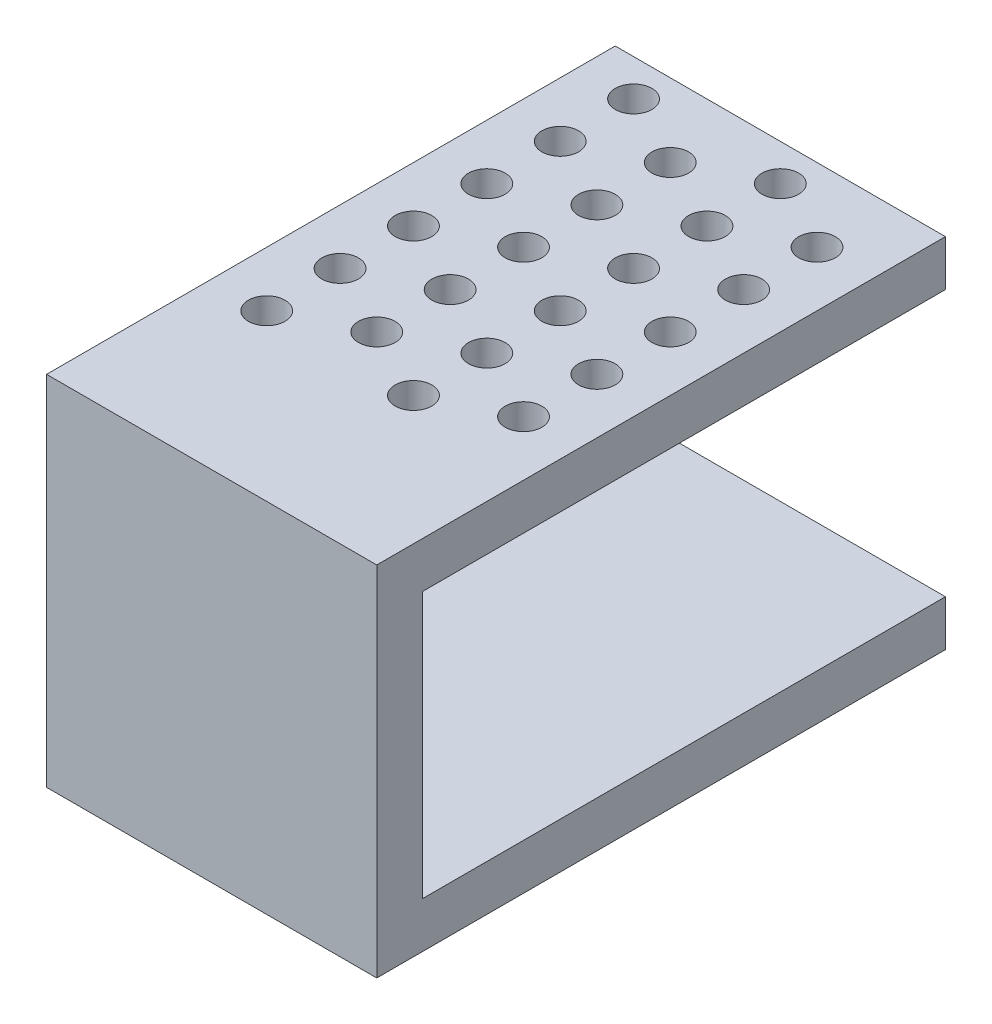
SolidWorks part; units mm, degrees
ref_plane "Front Plane" through (0, 0, 0) normal (0, 0, 1) x (1, 0, 0)
ref_plane "Top Plane" through (0, 0, 0) normal (0, 1, 0) x (1, 0, 0)
ref_plane "Right Plane" through (0, 0, 0) normal (1, 0, 0) x (0, 0, -1)
sketch "Sketch2" plane through (0, 0, 0) normal (0, 1, 0) x (1, 0, 0)
  line L1 (-20, 16) -> (-2, 16)
  line L2 (-20, 16) -> (-20, -8)
  line L3 (-20, -8) -> (-2, -8)
  line L4 (-2, 16) -> (-2, -8)
  circle A0 centre (-17, -6) radius 1
  circle A1 centre (-17, -2) radius 1
  circle A2 centre (-17, 2) radius 1
  circle A3 centre (-17, 6) radius 1
  circle A4 centre (-17, 10) radius 1
  circle A5 centre (-17, 14) radius 1
  circle A6 centre (-13, -4) radius 1
  circle A7 centre (-13, 0) radius 1
  circle A8 centre (-13, 4) radius 1
  circle A9 centre (-13, 8) radius 1
  circle A10 centre (-13, 12) radius 1
  circle A11 centre (-9, -6) radius 1
  circle A12 centre (-9, -2) radius 1
  circle A13 centre (-9, 2) radius 1
  circle A14 centre (-9, 6) radius 1
  circle A15 centre (-9, 10) radius 1
  circle A16 centre (-9, 14) radius 1
  circle A17 centre (-5, -4) radius 1
  circle A18 centre (-5, 0) radius 1
  circle A19 centre (-5, 4) radius 1
  circle A20 centre (-5, 8) radius 1
  circle A21 centre (-5, 12) radius 1
  dimension "D1" = 24
  dimension "D2" = 18
extrude "Boss-Extrude2" add sketch "Sketch2" along normal blind 2.5
sketch "Sketch3" plane through (0, 0, 8) normal (0, 0, 1) x (1, 0, 0)
  line L1 (-20, 2.5) -> (-2, 2.5)
  line L2 (-20, 2.5) -> (-20, 0)
  line L3 (-20, 0) -> (-2, 0)
  line L4 (-2, 2.5) -> (-2, 0)
extrude "Boss-Extrude3" add sketch "Sketch3" along normal blind 7
sketch "Sketch4" plane through (0, 0, 0) normal (0, -1, 0) x (-1, 0, 0)
  line L0 (20, 16) -> (20, -15) construction
  line L1 (2, -15) -> (20, -15)
  line L2 (2, -15) -> (2, -12.5)
  line L3 (2, -12.5) -> (20, -12.5)
  line L4 (20, -15) -> (20, -12.5)
  dimension "D1" = 2.5
extrude "Boss-Extrude4" add sketch "Sketch4" along normal blind 17
sketch "Sketch5" plane through (0, 0, 12.5) normal (0, 0, -1) x (-1, 0, 0)
  line L0 (20, -17) -> (20, 0) construction
  line L1 (2, -17) -> (20, -17)
  line L2 (2, -17) -> (2, -14.5)
  line L3 (2, -14.5) -> (20, -14.5)
  line L4 (20, -17) -> (20, -14.5)
  dimension "D1" = 2.5
extrude "Boss-Extrude5" add sketch "Sketch5" along normal blind 28.5
